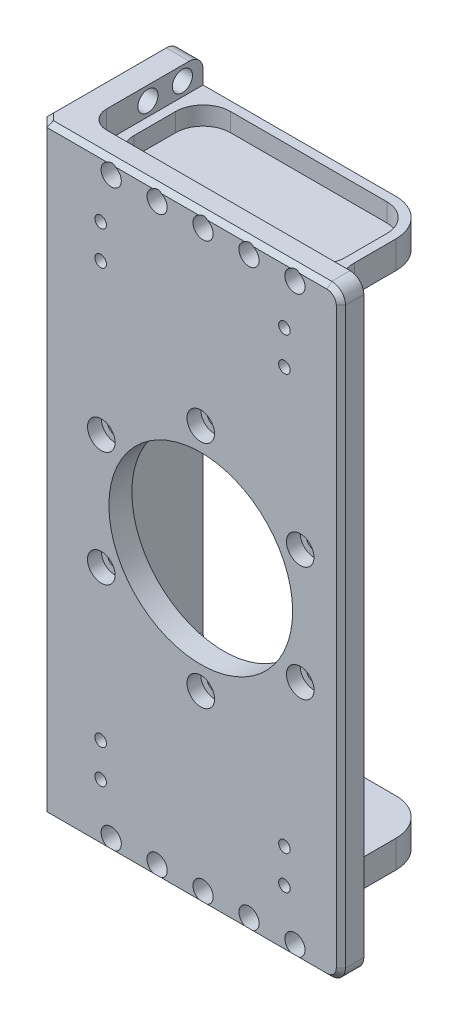
SolidWorks part; units mm, degrees
material "7075-T6 (SN)"
ref_plane "前视基准面" through (0, 0, 0) normal (0, 0, 1) x (1, 0, 0)
ref_plane "上视基准面" through (0, 0, 0) normal (0, 1, 0) x (1, 0, 0)
ref_plane "右视基准面" through (0, 0, 0) normal (1, 0, 0) x (0, 0, -1)
sketch "草图1" plane through (0, 0, 0) normal (0, 0, 1) x (1, 0, 0)
  line L0 (-237.1759, 120) -> (-237.1759, 1) construction
  line L1 (-237.1759, 60.5) -> (-177.1759, 60.5) construction
  line L2 (812.8241, 60.5) -> (-387.1759, 60.5) construction
  line L3 (-165.4601, -5) -> (-232.1759, -5) construction
  line L4 (-237.1759, 126) -> (-177.1759, 126)
  line L5 (-237.1759, 126) -> (-237.1759, -5)
  line L6 (-237.1759, -5) -> (-177.1759, -5)
  line L7 (-177.1759, 126) -> (-177.1759, -5)
extrude "凸台-拉伸1" add sketch "草图1" along normal blind 5
sketch "草图2" plane through (-237.1759, 0, 0) normal (-1, 0, 0) x (0, 0, 1)
  line L0 (-235, 126) -> (-5, 126) construction
  line L1 (5, -5) -> (-25, -5)
  line L2 (5, -5) -> (5, 126)
  line L3 (5, 126) -> (-25, 126)
  line L4 (-25, -5) -> (-25, 126)
extrude "凸台-拉伸2" add sketch "草图2" along normal blind 6
sketch "草图3" plane through (0, 0, 5) normal (0, 0, 1) x (1, 0, 0)
  line L2 (-236.1759, 60.5) -> (-179.1759, 60.5) construction
  circle A2 centre (-207.6759, 60.5) radius 28.5 construction
  circle A3 centre (-207.6759, 60.5) radius 25 construction
  circle A4 centre (-207.6759, 60.5) radius 20
  dimension "D1" = 5
extrude "切除-拉伸1" cut sketch "草图3" against normal blind 10
sketch "草图4" plane through (0, 0, 5) normal (0, 0, 1) x (1, 0, 0)
  line L4 (-177.1759, 126) -> (-243.1759, 126)
  line L5 (-243.1759, 126) -> (-243.1759, -5)
  line L6 (-243.1759, -5) -> (-177.1759, -5)
  line L7 (-177.1759, -5) -> (-177.1759, 126)
  line L8 (-177.1759, 126) -> (-243.1759, 126)
  line L9 (-243.1759, 126) -> (-243.1759, -5)
  line L10 (-243.1759, -5) -> (-177.1759, -5)
  line L11 (-177.1759, -5) -> (-177.1759, 126)
  circle A0 centre (-207.6759, 60.5) radius 20 construction
  circle A1 centre (-207.6759, 60.5) radius 20
  dimension "D1" = 0
chamfer "倒角1" distance 2 angle 45 1 edges at (-243.1759, 60.5, 5)
fillet "圆角1" radius 3 4 edges at (-240.1759, 126, -25) (-177.1759, 126, 2.5) (-177.1759, -5, 2.5) (-240.1759, -5, -25)
sketch "草图5" plane through (0, 0, 5) normal (0, 0, 1) x (1, 0, 0)
  circle A0 centre (-207.6759, 60.5) radius 25 construction
  point P3 (-207.6759, 85.5)
  point P4 (-186.0252, 73)
  point P7 (-186.0252, 48)
  point P8 (-207.6759, 35.5)
  point P9 (-229.3265, 48)
  point P10 (-229.3265, 73)
  point P11 (-207.6759, 60.5)
  dimension "D1" = 6
sketch "草图13" plane through (0, 0, 5) normal (0, 0, 1) x (1, 0, 0)
  circle A0 centre (-207.6759, 85.5) radius 1.6
  circle A1 centre (-229.3265, 73) radius 1.6
  circle A2 centre (-186.0252, 73) radius 1.6
  circle A3 centre (-186.0252, 48) radius 1.6
  circle A4 centre (-207.6759, 35.5) radius 1.6
  circle A5 centre (-229.3265, 48) radius 1.6
extrude "切除-拉伸2" cut sketch "草图13" against normal blind 6
sketch "草图14" plane through (0, 0, 5) normal (0, 0, 1) x (1, 0, 0)
  circle A0 centre (-207.6759, 85.5) radius 3
  circle A1 centre (-186.0252, 73) radius 3
  circle A2 centre (-186.0252, 48) radius 3
  circle A3 centre (-207.6759, 35.5) radius 3
  circle A4 centre (-229.3265, 48) radius 3
  circle A5 centre (-229.3265, 73) radius 3
extrude "切除-拉伸3" cut sketch "草图14" against normal blind 3
chamfer "倒角4" distance 1 angle 45 12 edges at (-242.1759, -5, 4) (-210.6759, -5, 5) (-243.1759, -5, -9.5) (-178.0545, -4.1213, 5) (-243.1759, -4.1213, -24.1213) (-177.1759, 60.5, 5) (-243.1759, 60.5, -25) (-178.0545, 125.1213, 5) (-243.1759, 125.1213, -24.1213) (-210.6759, 126, 5) (-242.1759, 126, 4) (-243.1759, 126, -9.5)
sketch "草图15" plane through (0, 0, 0) normal (0, -1, 0) x (1, 0, 0)
  line L0 (-11.5, -120) -> (-5.5, -120) construction
  line L1 (-11.5, -193) -> (-11.5, -47) construction
  line L2 (-5.5, -108) -> (-5.5, -132) construction
  line L3 (-8.5, -100) -> (-8.5, -140) construction
  line L4 (-8.5, -80) -> (-8.5, -160) construction
  line L5 (-8.5, -60) -> (-8.5, -180) construction
  point P9 (-8.5, -120)
  point P13 (-8.5, -120)
  point P16 (-8.5, -120)
sketch "草图16" plane through (0, 0, 0) normal (0, 0, -1) x (-1, 0, 0)
  line L5 (237.1759, 126) -> (237.1759, 120) construction
  line L6 (237.1759, 123) -> (237.1759, -2) construction
  line L8 (237.1759, 120) -> (187.1759, 120)
  line L9 (237.1759, 120) -> (237.1759, 114)
  line L10 (237.1759, 114) -> (187.1759, 114)
  line L11 (187.1759, 120) -> (187.1759, 114)
extrude "凸台-拉伸4" add sketch "草图16" along normal up to surface (25 mm away) up to face at (-239.6759, 60.5, -25)
ref_plane "基准面1" through (0, 60.5, 0) normal (0, -1, 0) x (-1, 0, 0)
mirror "镜向1" about plane through (0, 60.5, 0) normal (0, -1, 0) of "凸台-拉伸4"
fillet "圆角3" radius 4 2 edges at (-237.1759, -2, 0) (-237.1759, 123, 0)
fillet "圆角4" radius 10 2 edges at (-237.1759, 114, -12.5) (-237.1759, 7, -12.5)
fillet "圆角5" radius 8 4 edges at (-187.1759, 117, 0) (-187.1759, 117, -25) (-187.1759, 4, 0) (-187.1759, 4, -25)
sketch "草图17" plane through (0, 120, 0) normal (0, 1, 0) x (1, 0, 0)
  line L4 (-235.1759, 4) -> (-235.1759, 2)
  line L5 (-235.1759, 2) -> (-233.1759, 2)
  line L8 (-189.1759, 8) -> (-189.1759, 17)
  line L9 (-195.1759, 23) -> (-235.1759, 23)
  line L10 (-235.1759, 23) -> (-235.1759, 4)
  line L11 (-233.1759, 2) -> (-187.1759, 2)
  line L12 (-189.1759, 8) -> (-189.1759, 17)
  line L13 (-195.1759, 23) -> (-235.1759, 23)
  line L14 (-235.1759, 23) -> (-235.1759, 4)
  line L15 (-233.1759, 2) -> (-187.1759, 2)
  arc A6 (-189.1759, 17) -> (-195.1759, 23) centre (-195.1759, 17) ccw
  arc A7 (-235.1759, 4) -> (-233.1759, 2) centre (-233.1759, 4) ccw
  arc A8 (-189.1759, 8) -> (-187.1759, 2) centre (-179.1759, 8) ccw
  arc A9 (-189.1759, 17) -> (-195.1759, 23) centre (-195.1759, 17) ccw
  arc A11 (-189.1759, 8) -> (-187.1759, 2) centre (-179.1759, 8) ccw
  dimension "D1" = 2
extrude "切除-拉伸4" cut sketch "草图17" against normal blind 4
mirror "镜向2" about plane through (0, 60.5, 0) normal (0, -1, 0) of "切除-拉伸4"
fillet "圆角6" radius 6 10 edges at (-235.1759, 118, -2) (-235.1759, 118, -23) (-188.6627, 116, -4.8377) (-187.1759, 118, -2) (-188.6627, 120, -4.8377) (-235.1759, 3, -2) (-188.6627, 1, -4.8377) (-187.1759, 3, -2) (-235.1759, 3, -23) (-188.6627, 5, -4.8377)
sketch "草图19" plane through (0, 0, 5) normal (0, 0, 1) x (1, 0, 0)
  line L0 (-243.1759, -5) -> (-237.1759, -5) construction
  line L1 (-243.1759, -5) -> (-177.1759, -5) construction
  line L2 (-237.1759, -5) -> (-177.1759, -5) construction
  line L3 (-207.1759, -5) -> (-207.1759, 1) construction
  line L4 (-217.1759, -2) -> (-197.1759, -2)
  line L5 (-227.1759, -2) -> (-187.1759, -2)
  circle A0 centre (-227.1759, -2) radius 2.2
  circle A1 centre (-217.1759, -2) radius 2.2
  circle A2 centre (-207.1759, -2) radius 2.2
  circle A3 centre (-197.1759, -2) radius 2.2
  circle A4 centre (-187.1759, -2) radius 2.2
  point P13 (-207.1759, -2)
  point P15 (-207.1759, -2)
extrude "切除-拉伸5" cut sketch "草图19" against normal blind 18
mirror "镜向3" about plane through (0, 60.5, 0) normal (0, -1, 0) of "切除-拉伸5"
sketch "草图20" plane through (-243.1759, 0, 0) normal (-1, 0, 0) x (0, 0, 1)
  line L0 (5, -5) -> (-1, -5) construction
  line L1 (5, -5) -> (5, 126) construction
  line L2 (4, -5) -> (2.5858, -5) construction
  line L3 (-1, -5) -> (-25, -5) construction
  line L4 (-5, -5) -> (-235, -5) construction
  line L5 (-13, -5) -> (-13, 1) construction
  line L6 (-20.5, -2) -> (-5.5, -2) construction
  circle A0 centre (-20.5, -2) radius 2.2
  circle A1 centre (-13, -2) radius 2.2
  point P15 (-13, -2)
extrude "切除-拉伸6" cut sketch "草图20" against normal blind 18
mirror "镜向4" about plane through (0, 60.5, 0) normal (0, -1, 0) of "切除-拉伸6"
sketch "草图21" plane through (0, 0, 5) normal (0, 0, 1) x (1, 0, 0)
  line L0 (-207.6759, 60.5) -> (-209.4659, 60.5)
  line L1 (-14.3, 60.5) -> (14.3, 60.5) construction
  line L2 (-209.4659, 60.5) -> (-209.4659, 64.19)
  line L4 (-229.4659, 113.065) -> (-189.4659, 113.065)
  line L5 (-229.4659, 113.065) -> (-229.4659, 15.315)
  line L6 (-229.4659, 15.315) -> (-189.4659, 15.315)
  line L7 (-189.4659, 113.065) -> (-189.4659, 15.315)
  line L8 (-229.4659, 113.065) -> (-189.4659, 15.315) construction
  line L9 (-229.4659, 15.315) -> (-189.4659, 113.065) construction
hole_wizard "M3 螺纹孔1" positions "草图22" profile "草图23" tap size "M3" standard "GB"
sketch "草图22" plane through (0, 0, 5) normal (0, 0, 1) x (1, 0, 0)
  point P0 (-229.4659, 113.065)
  point P3 (-189.4659, 113.065)
  point P6 (-189.4659, 15.315)
  point P9 (-229.4659, 15.315)
sketch "草图23" plane through (-229.4659, 113.065, 5) normal (1, 0, 0) x (0, -1, 0)
  line L0 (0, 0) -> (0, 8.2511)
  line L1 (0, 8.2511) -> (1.25, 7.5)
  line L2 (1.25, 7.5) -> (1.25, 0)
  line L5 (1.25, 0) -> (0, 0)
  line L10 (0, 8.2511) -> (-1.25, 7.5) construction
  line L11 (0, -6.35) -> (0, 107.95) construction
  dimension "螺纹孔钻头直径" = 2.5
  dimension "螺纹孔钻头深度" = 7.5
  dimension "导头角度" = 118
cosmetic thread "孔螺蚊线1" parameters "D1"=6, "D2"=3
cosmetic thread "孔螺蚊线2" parameters "D1"=6, "D2"=3
cosmetic thread "孔螺蚊线3" parameters "D1"=6, "D2"=3
cosmetic thread "孔螺蚊线4" parameters "D1"=6, "D2"=3
mirror "镜向5" about plane through (0, 60.5, 0) normal (0, -1, 0) of "M3 螺纹孔1"
cosmetic thread "孔螺蚊线5" parameters "D1"=6, "D2"=3
cosmetic thread "孔螺蚊线6" parameters "D1"=6, "D2"=3
cosmetic thread "孔螺蚊线7" parameters "D1"=6, "D2"=3
cosmetic thread "孔螺蚊线8" parameters "D1"=6, "D2"=3
sketch "草图24" plane through (-243.1759, 0, 0) normal (-1, 0, 0) x (0, 0, 1)
  line L0 (5, 60.5) -> (-7.12, 60.5)
  line L3 (-14.3, 60.5) -> (14.3, 60.5) construction
  line L4 (-7.12, 60.5) -> (-7.12, 35.2)
  line L5 (-7.12, 60.5) -> (-7.12, 85.8)
hole_wizard "M3 螺纹孔2" positions "草图25" profile "草图26" tap size "M3" standard "GB"
sketch "草图25" plane through (-243.1759, 0, 0) normal (-1, 0, 0) x (0, 0, 1)
  point P0 (-7.12, 85.8)
  point P3 (-7.12, 35.2)
sketch "草图26" plane through (-243.1759, 85.8, -7.12) normal (0, 1, 0) x (0, 0, 1)
  line L0 (0, 0) -> (0, 8.2511)
  line L1 (0, 8.2511) -> (1.25, 7.5)
  line L2 (1.25, 7.5) -> (1.25, 0)
  line L5 (1.25, 0) -> (0, 0)
  line L10 (0, 8.2511) -> (-1.25, 7.5) construction
  line L11 (0, -6.35) -> (0, 107.95) construction
  dimension "螺纹孔钻头直径" = 2.5
  dimension "螺纹孔钻头深度" = 7.5
  dimension "导头角度" = 118
cosmetic thread "孔螺蚊线9" parameters "D1"=6, "D2"=3
cosmetic thread "孔螺蚊线10" parameters "D1"=6, "D2"=3
